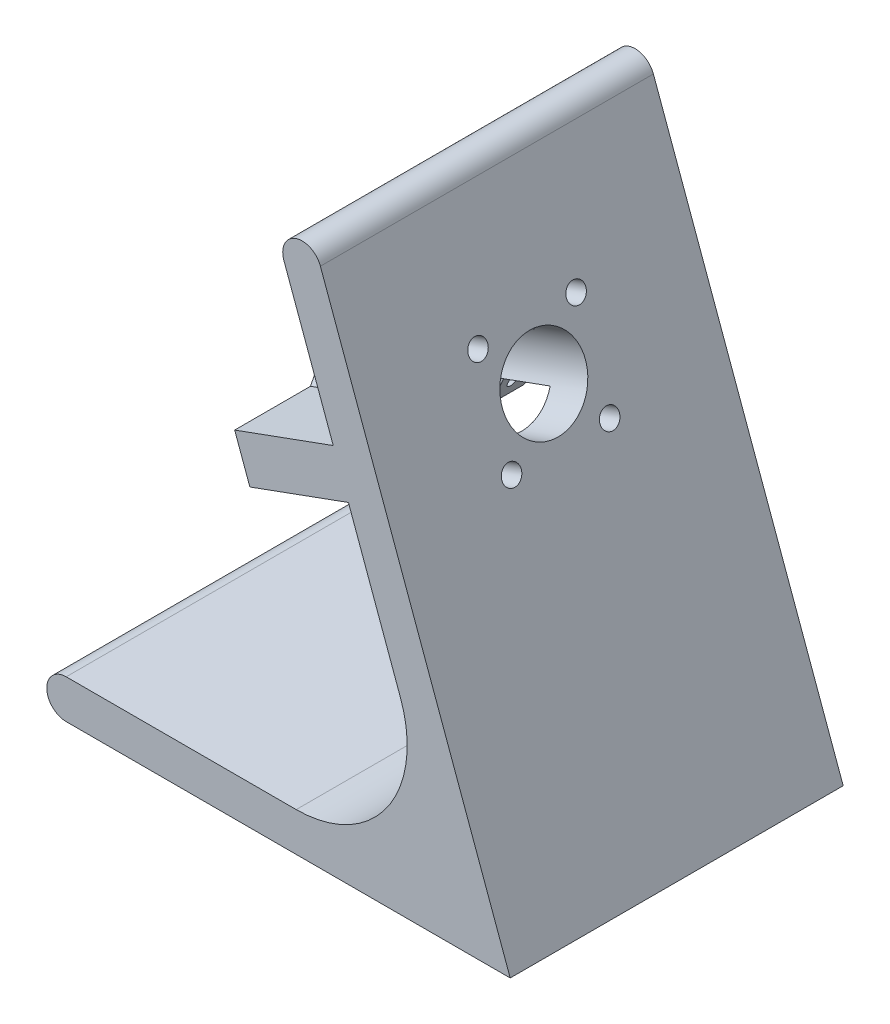
SolidWorks part; units mm, degrees
ref_plane "Front Plane" through (0, 0, 0) normal (0, 0, 1) x (1, 0, 0)
ref_plane "Top Plane" through (0, 0, 0) normal (0, 1, 0) x (1, 0, 0)
ref_plane "Right Plane" through (0, 0, 0) normal (1, 0, 0) x (0, 0, -1)
sketch "Sketch1" plane through (0, 0, 0) normal (0, 0, 1) x (1, 0, 0)
  line L0 (-91.0558, 0) -> (120.8515, 0) construction
  line L1 (0, 0) -> (80, 0)
  line L2 (80, 0) -> (45.798, 93.9693)
  line L3 (0, 7) -> (41.44, 7)
  line L4 (60.2339, 33.8404) -> (39.2201, 91.5751)
  line L5 (0, 7) -> (70.003, 7) construction
  line L6 (70.003, 7) -> (39.2201, 91.5751) construction
  arc A0 (0, 0) -> (0, 7) centre (0, 3.5) cw
  arc A1 (45.798, 93.9693) -> (39.2201, 91.5751) centre (42.5091, 92.7722) ccw
  arc A2 (41.44, 7) -> (60.2339, 33.8404) centre (41.44, 27) ccw
  dimension "D5" = 20
  dimension "D1" = 70
  dimension "D2" = 80
  dimension "D3" = 100
  dimension "D4" = 7
extrude "Boss-Extrude1" add sketch "Sketch1" along normal blind 60
sketch "Sketch2" plane through (70.6418, 25.7115, 0) normal (0.9397, 0.342, 0) x (0, 0, -1)
  line L0 (-30, 72.6384) -> (-30, -27.3616) construction
  line L1 (-60, 72.6384) -> (0, 72.6384) construction
  line L2 (-60, -27.3616) -> (0, -27.3616) construction
  line L3 (-60, 42.6384) -> (0, 42.6384) construction
  line L4 (-60, -27.3616) -> (-60, 72.6384) construction
  line L5 (0, -27.3616) -> (0, 72.6384) construction
  circle A0 centre (-30, 42.6384) radius 7.5
  dimension "D2" = 15
  dimension "D1" = 30
extrude "Cut-Extrude1" cut sketch "Sketch2" against normal through all
sketch "Sketch3" plane through (64.0639, 23.3174, 0) normal (-0.9397, -0.342, 0) x (0, 0, 1)
  circle A0 centre (21.1612, 33.7996) radius 1.75
  circle A1 centre (21.1612, 51.4772) radius 1.75
  circle A2 centre (38.8388, 51.4772) radius 1.75
  circle A3 centre (38.8388, 33.7996) radius 1.75
  dimension "D1" = 3.5
  dimension "D2" = 3.5
  dimension "D3" = 3.5
  dimension "D4" = 3.5
extrude "Cut-Extrude2" cut sketch "Sketch3" against normal through all
chamfer "Chamfer1" distance 2 angle 30 4 edges at (53.1023, 53.4341, 38.8388) (53.1023, 53.4341, 21.1612) (47.0562, 70.0457, 38.8388) (47.0562, 70.0457, 21.1612) first distance on face at (47.0562, 70.0457, 21.1612)
sketch "Sketch4" plane through (64.0639, 23.3174, 0) normal (-0.9397, -0.342, 0) x (0, 0, 1)
  line L0 (0, 42.6384) -> (60, 42.6384) construction
  line L1 (0, 72.6384) -> (0, 11.1984) construction
  line L2 (60, 72.6384) -> (60, 11.1984) construction
  line L3 (36.3443, 46.6384) -> (60, 46.6384)
  line L4 (0, 38.6384) -> (23.6557, 38.6384)
  line L5 (0, 38.6384) -> (0, 46.6384)
  line L6 (0, 46.6384) -> (23.6557, 46.6384)
  line L7 (60, 38.6384) -> (60, 46.6384)
  line L8 (0, 38.6384) -> (60, 46.6384) construction
  line L9 (0, 46.6384) -> (60, 38.6384) construction
  line L10 (36.3443, 38.6384) -> (60, 38.6384)
  circle A0 centre (30, 42.6384) radius 7.5 construction
  arc A1 (23.6557, 46.6384) -> (23.6557, 38.6384) centre (30, 42.6384) ccw
  arc A2 (36.3443, 38.6384) -> (36.3443, 46.6384) centre (30, 42.6384) ccw
  point P7 (30, 42.6384)
  dimension "D1" = 8
extrude "Boss-Extrude2" add sketch "Sketch4" along normal up to surface (18.9 mm away)
sketch "Sketch5" plane through (46.3037, 16.8532, 0) normal (-0.9397, -0.342, 0) x (0, 0, 1)
  line L0 (30, 50.1384) -> (30, 28.6384) construction
  line L1 (23.6557, 46.6384) -> (18.6557, 46.6384)
  line L2 (23.6557, 46.6384) -> (23.6557, 50.6384)
  line L3 (23.6557, 50.6384) -> (18.6557, 50.6384)
  line L4 (18.6557, 46.6384) -> (18.6557, 50.6384)
  line L5 (40, 28.6384) -> (20, 28.6384) construction
  line L6 (27.4, 42.6384) -> (32.6, 42.6384) construction
  line L7 (27.4, 40.4884) -> (27.4, 44.7884) construction
  line L8 (32.6, 44.7884) -> (32.6, 40.4884) construction
  line L9 (36.3443, 46.6384) -> (36.3443, 50.6384)
  line L10 (36.3443, 46.6384) -> (41.3443, 46.6384)
  line L11 (41.3443, 46.6384) -> (41.3443, 50.6384)
  line L12 (36.3443, 50.6384) -> (41.3443, 50.6384)
  line L13 (41.3443, 38.6384) -> (41.3443, 34.6384)
  line L14 (36.3443, 34.6384) -> (41.3443, 34.6384)
  line L15 (36.3443, 38.6384) -> (36.3443, 34.6384)
  line L16 (36.3443, 38.6384) -> (41.3443, 38.6384)
  line L17 (23.6557, 38.6384) -> (18.6557, 38.6384)
  line L18 (18.6557, 38.6384) -> (18.6557, 34.6384)
  line L19 (23.6557, 34.6384) -> (18.6557, 34.6384)
  line L20 (23.6557, 38.6384) -> (23.6557, 34.6384)
  circle A0 centre (21, 48.1384) radius 1
  arc A1 (36.3443, 46.6384) -> (23.6557, 46.6384) centre (30, 42.6384) ccw construction
  circle A2 centre (39, 48.1384) radius 1
  circle A3 centre (39, 37.1384) radius 1
  circle A4 centre (21, 37.1384) radius 1
  dimension "D3" = 2
  dimension "D1" = 5
  dimension "D2" = 4
extrude "Boss-Extrude3" add sketch "Sketch5" against normal blind 5
chamfer "Chamfer2" distance 5 angle 45 8 edges at (37.7871, 54.8715, 38.8443) (35.4379, 54.0164, 41.3443) (37.7871, 54.8715, 21.1557) (35.4379, 54.0164, 18.6557) (32.7017, 61.534, 18.6557) (35.0509, 62.389, 21.1557) (35.0509, 62.389, 38.8443) (32.7017, 61.534, 41.3443)
